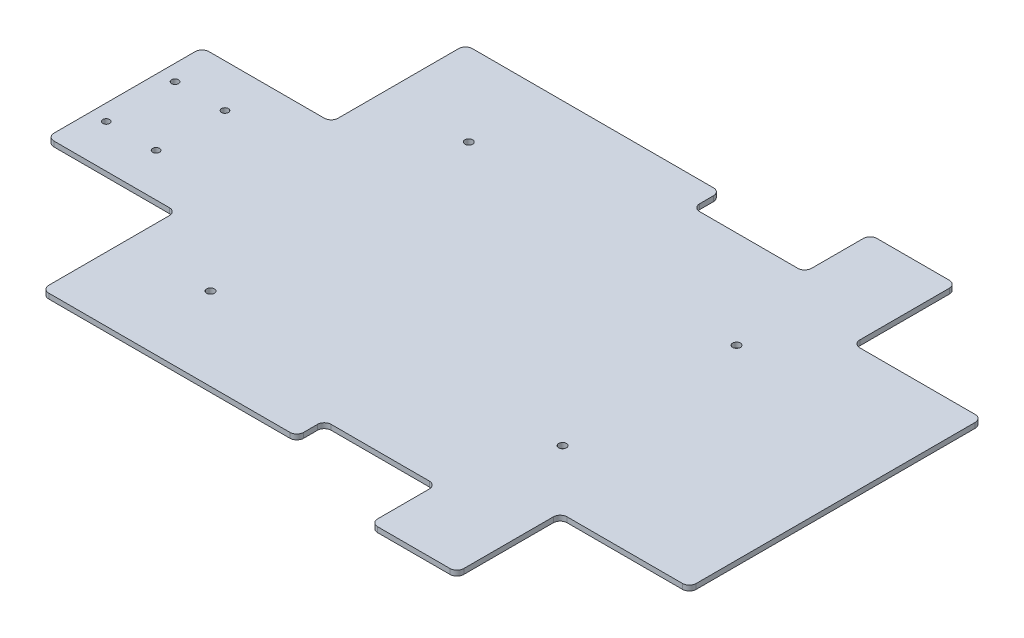
SolidWorks part; units mm, degrees
material "Aleación 1060"
ref_plane "Alzado" through (0, 0, 0) normal (0, 0, 1) x (1, 0, 0)
ref_plane "Planta" through (0, 0, 0) normal (0, 1, 0) x (1, 0, 0)
ref_plane "Vista lateral" through (0, 0, 0) normal (1, 0, 0) x (0, 0, -1)
sketch "Croquis1" plane through (0, 0, 0) normal (0, 1, 0) x (1, 0, 0)
  line L0 (0, 0) -> (-413, 0)
  line L1 (-413, 0) -> (-413, 45)
  line L2 (-413, 45) -> (-338, 45)
  line L3 (-338, 45) -> (-338, 123)
  line L4 (-338, 123) -> (-190, 123)
  line L5 (-190, 123) -> (-190, 107)
  line L6 (-190, 107) -> (-125, 107)
  line L7 (-125, 107) -> (-125, 145)
  line L8 (-125, 145) -> (-75, 145)
  line L9 (-75, 145) -> (-75, 85)
  line L10 (0, 0) -> (0, 85)
  line L11 (0, 85) -> (-75, 85)
  dimension "D1" = 413
  dimension "D2" = 45
  dimension "D3" = 75
  dimension "D4" = 123
  dimension "D5" = 148
  dimension "D6" = 16
  dimension "D7" = 50
  dimension "D8" = 85
  dimension "D9" = 65
  dimension "D10" = 60
extrude "Saliente-Extruir1" add sketch "Croquis1" along normal blind 3
mirror "Simetría1" about plane through (0, 3, 0) normal (0, 0, -1) of "Saliente-Extruir1"
fillet "Redondeo1" radius 4 20 edges at (-413, 1.5, -45) (-338, 1.5, -45) (-338, 1.5, -123) (-190, 1.5, -123) (-190, 1.5, -107) (-125, 1.5, -107) (-125, 1.5, -145) (-75, 1.5, -85) (-75, 1.5, -145) (0, 1.5, -85) (0, 1.5, 85) (-75, 1.5, 85) (-75, 1.5, 145) (-125, 1.5, 145) (-125, 1.5, 107) (-190, 1.5, 107) (-190, 1.5, 123) (-338, 1.5, 123) (-338, 1.5, 45) (-413, 1.5, 45)
sketch "Croquis2" plane through (0, 3, 0) normal (0, 1, 0) x (1, 0, 0)
  line L0 (-413, 0) -> (0, 0) construction
  line L1 (-413, 41) -> (-413, -41) construction
  line L2 (0, -81) -> (0, 81) construction
  line L3 (-214.7209, -131) -> (31.1095, -131) construction
  line L4 (-214.0485, -154) -> (44.3152, -154) construction
  line L5 (-79, -145) -> (-121, -145) construction
  line L6 (-44, -177) -> (-156, -177)
  line L7 (-44, -177) -> (-44, -131)
  line L8 (-44, -131) -> (-156, -131)
  line L9 (-156, -177) -> (-156, -131)
  line L10 (-44, -177) -> (-156, -131) construction
  line L11 (-44, -131) -> (-156, -177) construction
  line L12 (-156, 154) -> (-44, 154) construction
  line L13 (-374, -177) -> (-486, -177)
  line L14 (-374, -177) -> (-374, -131)
  line L15 (-374, -131) -> (-486, -131)
  line L16 (-486, -177) -> (-486, -131)
  line L17 (-374, -177) -> (-486, -131) construction
  line L18 (-374, -131) -> (-486, -177) construction
  line L19 (-44, 177) -> (-156, 177)
  line L20 (-44, 177) -> (-44, 131)
  line L21 (-44, 131) -> (-156, 131)
  line L22 (-156, 177) -> (-156, 131)
  line L23 (-374, 131) -> (-486, 177) construction
  line L24 (-374, 177) -> (-486, 131) construction
  line L25 (-486, 177) -> (-486, 131)
  line L26 (-374, 131) -> (-486, 131)
  line L27 (-374, 177) -> (-374, 131)
  line L28 (-374, 177) -> (-486, 177)
  line L29 (-430, -154) -> (-430, 154) construction
  point P10 (-100, -154)
  point P17 (-100, -145)
  point P20 (-430, -154)
  point P33 (-430, 154)
  dimension "D1" = 131
  dimension "D2" = 154
  dimension "D3" = 46
  dimension "D4" = 112
  dimension "D5" = 330
  dimension "D6" = 308
sketch "Croquis3" plane through (0, 3, 0) normal (0, 1, 0) x (1, 0, 0)
  line L0 (-100, -145) -> (-100, 145) construction
  line L1 (-79, -145) -> (-121, -145) construction
  line L2 (-79, 145) -> (-121, 145) construction
  line L3 (-161.61, 16.8885) -> (-161.61, -25.475) construction
  line L4 (-232.2, 27.5722) -> (-232.2, -25.475) construction
  dimension "D1" = 132.2
  dimension "D2" = 61.61
ref_plane "Plano1" [suppressed] through (-430, 0, 0) normal (1, 0, 0) x (0, 0, -1)
sketch "Croquis4" plane through (0, 3, 0) normal (0, 1, 0) x (1, 0, 0)
  circle A0 centre (-108.1, -50.5) radius 2.25
  dimension "D1" = 4.5
extrude "Cortar-Extruir1" cut sketch "Croquis4" against normal blind 10
mirror "Simetría2" about plane through (0, 0, 0) normal (0, 0, 1) of "Cortar-Extruir1"
sketch "Croquis5" plane through (0, 3, 0) normal (0, 1, 0) x (1, 0, 0)
  circle A0 centre (-288.1, -75) radius 2.25
  dimension "D1" = 4.5
extrude "Cortar-Extruir2" cut sketch "Croquis5" against normal blind 10
mirror "Simetría3" about plane through (0, 0, 0) normal (0, 0, 1) of "Cortar-Extruir2"
sketch "Croquis6" plane through (0, 3, 0) normal (0, 1, 0) x (1, 0, 0)
  line L0 (-413, 0) -> (0, 0) construction
  line L1 (-413, 41) -> (-413, -41) construction
  circle A0 centre (-374.7, 20) radius 2
  circle A1 centre (-403.7, 20) radius 2
  circle A2 centre (-374.7, -19.999) radius 2
  circle A3 centre (-403.7, -19.999) radius 2
  dimension "D1" = 4
  dimension "D2" = 29
  dimension "D3" = 39.999
  dimension "D4" = 20
  dimension "D5" = 9.3
extrude "Cortar-Extruir3" cut sketch "Croquis6" against normal blind 4
